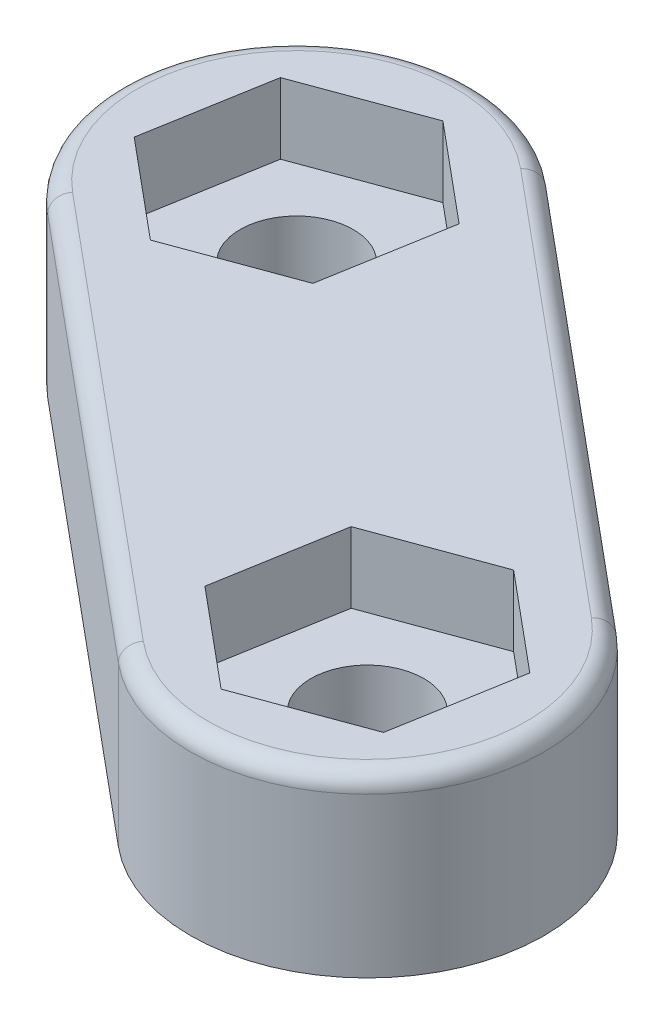
SolidWorks part; units mm, degrees
ref_plane "Front Plane" through (0, 0, 0) normal (0, 0, 1) x (1, 0, 0)
ref_plane "Top Plane" through (0, 0, 0) normal (0, 1, 0) x (1, 0, 0)
ref_plane "Right Plane" through (0, 0, 0) normal (1, 0, 0) x (0, 0, -1)
sketch "Sketch1" plane through (0, 0, 0) normal (0, 1, 0) x (1, 0, 0)
  line L0 (-9.2009, 1.1589) -> (2.7991, -8.8411)
  line L1 (-6, 5) -> (6, 5)
  line L2 (-6, 5) -> (-6, -5)
  line L3 (-6, -5) -> (6, -5)
  line L4 (6, 5) -> (6, -5)
  line L5 (-6, 5) -> (6, -5) construction
  line L6 (-6, -5) -> (6, 5) construction
  line L7 (-2.7991, 8.8411) -> (9.2009, -1.1589)
  circle A0 centre (-6, 5) radius 5
  circle A1 centre (6, -5) radius 5
  circle A2 centre (-6, 5) radius 1.6
  circle A3 centre (6, -5) radius 1.6
  point P0 (0, 0)
  dimension "D3" = 10
  dimension "D4" = 3.2
  dimension "D1" = 12
  dimension "D2" = 10
extrude "Boss-Extrude1" add sketch "Sketch1" along normal blind 5 contours A2 L1 A0 L2 | A2 L2 A0 L1 | A1 L4 L7 L1 A0 L2 L0 L3 | A3 L4 A1 L3 | A3 L3 A1 L4 | A1 L3 L0 | A0 L0 L2 | A1 L7 L4 | A0 L1 L7 region at (-6.8409, 0, 0.3462) region at (-9.7325, 0, -8.1104) region at (0, 0, 0) region at (-0.3085, 0, -6.0405) region at (-3.7133, 0, -2.7133) region at (0.3085, 0, 6.0405) region at (1.6001, 0, 7.0608) region at (3.7133, 0, 2.7133) region at (6.8409, 0, -0.3462)
sketch "Sketch2" plane through (0, 5, 0) normal (0, 1, 0) x (1, 0, 0)
  line L0 (-9.2009, 1.1589) -> (2.7991, -8.8411) construction
  line L1 (-8.7499, 7.2916) -> (-9.3595, 3.7643)
  line L2 (-9.3595, 3.7643) -> (-6.6096, 1.4727)
  line L3 (-6.6096, 1.4727) -> (-3.2501, 2.7084)
  line L4 (-3.2501, 2.7084) -> (-2.6405, 6.2357)
  line L5 (-2.6405, 6.2357) -> (-5.3904, 8.5273)
  line L6 (-5.3904, 8.5273) -> (-8.7499, 7.2916)
  line L7 (3.2009, 3.8411) -> (-3.2009, -3.8411) construction
  line L8 (-2.7991, 8.8411) -> (9.2009, -1.1589) construction
  line L9 (5.3904, -8.5273) -> (2.6405, -6.2357)
  line L10 (8.7499, -7.2916) -> (5.3904, -8.5273)
  line L11 (9.3595, -3.7643) -> (8.7499, -7.2916)
  line L12 (6.6096, -1.4727) -> (9.3595, -3.7643)
  line L13 (3.2501, -2.7084) -> (6.6096, -1.4727)
  line L14 (2.6405, -6.2357) -> (3.2501, -2.7084)
  circle A0 centre (-6, 5) radius 3.1 construction
  dimension "D1" = 6.2
extrude "Cut-Extrude1" cut sketch "Sketch2" against normal blind 2
fillet "Fillet1" radius 0.5 4 edges at (-9.8411, 5, -8.2009) (3.2009, 5, -3.8411) (9.8411, 5, 8.2009) (-3.2009, 5, 3.8411)
